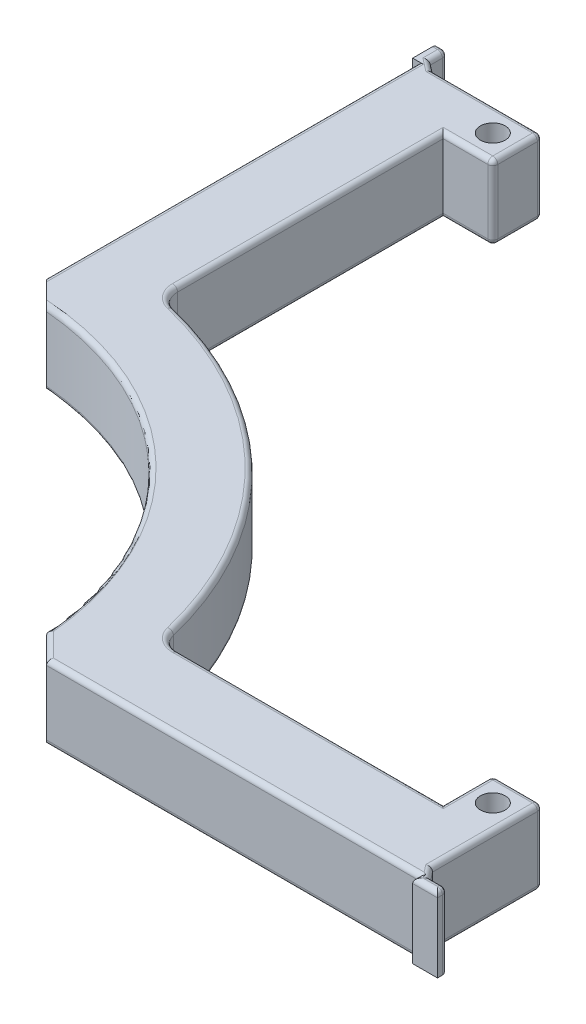
SolidWorks part; units mm, degrees
ref_plane "Front Plane" through (0, 0, 0) normal (0, 0, 1) x (1, 0, 0)
ref_plane "Top Plane" through (0, 0, 0) normal (0, 1, 0) x (1, 0, 0)
ref_plane "Right Plane" through (0, 0, 0) normal (1, 0, 0) x (0, 0, -1)
sketch "Sketch1" plane through (0, 0, 0) normal (0, 1, 0) x (1, 0, 0)
  line L0 (0, 0) -> (0, -6.35)
  line L1 (0, -6.35) -> (1.4732, -6.35)
  line L2 (1.4732, -6.35) -> (1.4732, -107.95)
  line L3 (1.4732, -186.69) -> (169.2079, -18.9553) construction
  line L4 (0, 0) -> (2.54, 0)
  line L5 (2.54, 0) -> (2.54, -4.3818)
  line L6 (2.54, -4.3818) -> (5.08, -6.35)
  line L7 (5.08, -6.35) -> (33.2232, -6.35)
  line L8 (33.2232, -6.35) -> (33.2232, -19.05)
  line L9 (33.2232, -19.05) -> (20.5232, -19.05)
  line L10 (20.5232, -19.05) -> (20.5232, -91.1619)
  line L12 (169.1132, -167.64) -> (97.0013, -167.64)
  line L13 (169.1132, -154.94) -> (169.1132, -167.64)
  line L14 (181.8132, -154.94) -> (169.1132, -154.94)
  line L15 (181.8132, -183.0832) -> (181.8132, -154.94)
  line L16 (183.7814, -185.6232) -> (181.8132, -183.0832)
  line L17 (188.1632, -185.6232) -> (183.7814, -185.6232)
  line L18 (188.1632, -188.1632) -> (188.1632, -185.6232)
  line L19 (188.1632, -188.1632) -> (181.8132, -188.1632)
  line L20 (181.8132, -188.1632) -> (181.8132, -186.69)
  line L21 (181.8132, -186.69) -> (80.2132, -186.69)
  arc A0 (1.4732, -107.95) -> (80.2132, -186.69) centre (1.4732, -186.69) cw
  arc A1 (20.5232, -91.1619) -> (97.0013, -167.64) centre (1.4732, -186.69) cw
  circle A2 centre (26.8732, -12.7) radius 3.175
  circle A3 centre (175.4632, -161.29) radius 3.175
  dimension "D4" = 78.74
  dimension "D5" = 0
  dimension "D7" = 97.409
  dimension "D15" = 6.35
  dimension "D1" = 0
  dimension "D2" = 45
  dimension "D6" = 19.05
  dimension "D8" = 1.4732
  dimension "D9" = 6.35
  dimension "D10" = 2.54
  dimension "D11" = 0
  dimension "D12" = 2.54
  dimension "D13" = 12.7
  dimension "D14" = 12.7
  dimension "D16" = 6.35
  dimension "D17" = 6.35
  dimension "D18" = 101.6
extrude "Boss-Extrude1" add sketch "Sketch1" along normal blind 19.05
chamfer "Chamfer1" distance 6.35 angle 45 2 edges at (80.2132, 9.525, 186.69) (1.4732, 9.525, 107.95)
fillet "Fillet1" radius 5.08 2 edges at (97.0013, 9.525, 167.64) (20.5232, 9.525, 91.1619)
fillet "Fillet2" radius 1.27 45 edges at (135.0972, 0, 167.64) (97.9402, 0, 166.5526) (20.5232, 0, 53.066) (21.6106, 0, 90.223) (135.0972, 19.05, 167.64) (97.9402, 19.05, 166.5526) (20.5232, 19.05, 53.066) (21.6106, 19.05, 90.223) (188.1632, 9.525, 185.6232) (185.9723, 0, 185.6232) (182.7973, 0, 184.3532) (169.1132, 0, 161.29) (175.4632, 0, 154.94) (181.8132, 0, 169.0116) (169.1132, 9.525, 154.94) (181.8132, 9.525, 154.94) (33.2232, 0, 12.7) (33.2232, 9.525, 19.05) (33.2232, 19.05, 12.7) (33.2232, 9.525, 6.35) (19.1516, 0, 6.35) (19.1516, 19.05, 6.35) (26.8732, 19.05, 19.05) (26.8732, 0, 19.05) (1.4732, 19.05, 53.975) (1.4732, 0, 53.975) (57.1508, 0, 131.0124) (181.8132, 19.05, 187.4266) (184.9882, 19.05, 188.1632) (188.1632, 19.05, 186.8932) (182.7973, 19.05, 184.3532) (185.9723, 19.05, 185.6232) (181.8132, 19.05, 169.0116) (175.4632, 19.05, 154.94) (169.1132, 19.05, 161.29) (83.2484, 19.05, 183.3752) (134.1882, 19.05, 186.69) (57.1508, 19.05, 131.0124) (70.3518, 0, 117.8114) (70.3518, 19.05, 117.8114) (2.54, 0, 2.1909) (1.27, 19.05, 0) (3.81, 19.05, 5.3659) (2.54, 19.05, 2.1909) (2.54, 9.525, 0)
fillet "Fillet3" radius 1.27 1 edges at (134.1882, 0, 186.69)
